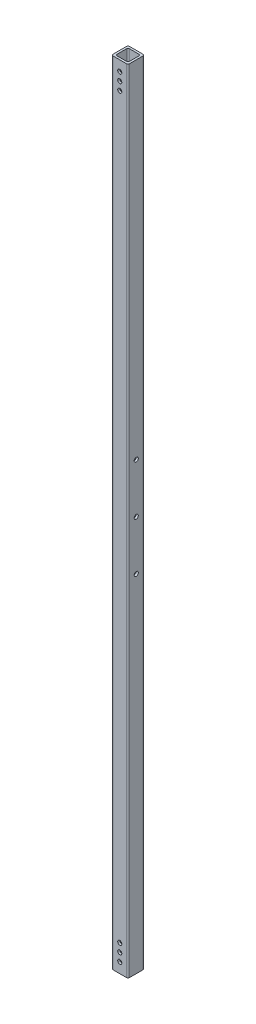
SolidWorks part; units mm, degrees
material "6061-T6 (SS)"
ref_plane "Front Plane" through (0, 0, 0) normal (0, 0, 1) x (1, 0, 0)
ref_plane "Top Plane" through (0, 0, 0) normal (0, 1, 0) x (1, 0, 0)
ref_plane "Right Plane" through (0, 0, 0) normal (1, 0, 0) x (0, 0, -1)
sketch "Sketch1" plane through (0, 0, 0) normal (0, 1, 0) x (1, 0, 0)
  line L0 (9.525, 9.525) -> (-9.525, 9.525)
  line L1 (12.7, -12.7) -> (-12.7, -12.7)
  line L2 (12.7, -12.7) -> (12.7, 12.7)
  line L3 (12.7, 12.7) -> (-12.7, 12.7)
  line L4 (-12.7, -12.7) -> (-12.7, 12.7)
  line L5 (12.7, -12.7) -> (-12.7, 12.7) construction
  line L6 (12.7, 12.7) -> (-12.7, -12.7) construction
  line L7 (-9.525, -9.525) -> (-9.525, 9.525)
  line L8 (9.525, -9.525) -> (-9.525, -9.525)
  line L9 (9.525, -9.525) -> (9.525, 9.525)
  point P0 (0, 0)
  dimension "D1" = 25.4
  dimension "D2" = 25.4
  dimension "D3" = 3.175
extrude "Boss-Extrude1" add sketch "Sketch1" along normal mid plane 1219.2
fillet "Fillet1" radius 2.1082 8 edges at (9.525, 0, -9.525) (-9.525, 0, -9.525) (-9.525, 0, 9.525) (9.525, 0, 9.525) (12.7, 0, -12.7) (-12.7, 0, -12.7) (-12.7, 0, 12.7) (12.7, 0, 12.7)
sketch "Sketch6" plane through (0, 0, -12.7) normal (0, 0, -1) x (-1, 0, 0)
  line L0 (0, 609.6) -> (0, 600.8737) construction
  line L2 (0, 402.295) -> (0, -606.425) construction
  line L3 (-10.5918, 609.6) -> (10.5918, 609.6) construction
  line L7 (0, 0) -> (10.5918, 0) construction
  line L8 (10.5918, -609.6) -> (10.5918, 609.6) construction
  line L9 (0, 609.6) -> (0, 558.8) construction
  circle A12 centre (0, 568.325) radius 3.175
  circle A13 centre (0, 581.025) radius 3.175
  circle A14 centre (0, 593.725) radius 3.175
  point P2 (0, 0)
  point P3 (0, 609.6)
  point P29 (0, 568.325)
  point P31 (0, 581.025)
  point P32 (0, 593.725)
  dimension "D1" = 12.7
  dimension "D2" = 12.7
  dimension "D3" = 15.875
  dimension "D7" = 50.8
extrude "Cut-Extrude5" cut sketch "Sketch6" against normal through all
sketch "Sketch7" plane through (-12.7, 0, 0) normal (-1, 0, 0) x (0, 0, 1)
  circle A0 centre (0, 0) radius 3.175
  dimension "D1" = 6.35
extrude "Cut-Extrude6" cut sketch "Sketch7" against normal through all
sketch "Sketch8" plane through (-12.7, 0, 0) normal (-1, 0, 0) x (0, 0, 1)
  line L0 (0, 0) -> (0, -76.2) construction
  circle A0 centre (0, -76.2) radius 3.175
  dimension "D2" = 6.35
  dimension "D1" = 76.2
extrude "Cut-Extrude7" cut sketch "Sketch8" against normal through all
mirror "Mirror1" about plane through (0, 0, 0) normal (0, 1, 0) of "Cut-Extrude7"
mirror "Mirror2" about plane through (0, 0, 0) normal (0, 1, 0) of "Cut-Extrude5"
